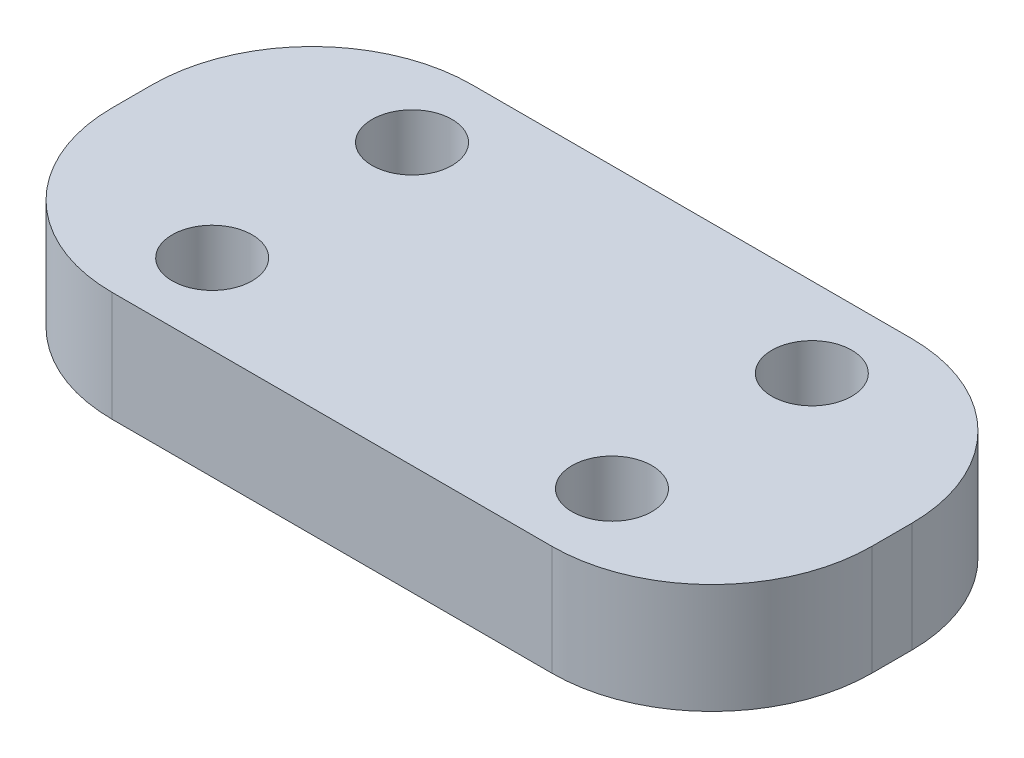
SolidWorks part; units mm, degrees
material "PETG-cf"
ref_plane "Plano frontal" through (0, 0, 0) normal (0, 0, 1) x (1, 0, 0)
ref_plane "Plano superior" through (0, 0, 0) normal (0, 1, 0) x (1, 0, 0)
ref_plane "Plano direito" through (0, 0, 0) normal (1, 0, 0) x (0, 0, -1)
sketch "Esboço1" plane through (0, 0, 0) normal (0, 1, 0) x (1, 0, 0)
  line L0 (-19, 0) -> (19, 0) construction
  line L1 (-19, -4) -> (19, -4)
  line L2 (-19, -4) -> (-19, 4)
  line L4 (19, -4) -> (19, 4)
  line L5 (-19, -4) -> (19, 4) construction
  line L6 (-19, 4) -> (19, -4) construction
  line L7 (0, 4) -> (0, -4) construction
  line L8 (-19, 4) -> (-19, 14)
  line L9 (-19, 14) -> (19, 14)
  line L10 (19, 14) -> (19, 4)
  line L11 (-10, 10) -> (10, 10) construction
  line L12 (-10, 0) -> (-10, 10) construction
  line L13 (10, 0) -> (10, 10) construction
  circle A0 centre (-10, 0) radius 2
  circle A1 centre (10, 0) radius 2
  circle A2 centre (-10, 10) radius 2
  circle A3 centre (10, 10) radius 2
  point P0 (0, 0)
  dimension "D3" = 4
  dimension "D6" = 4
  dimension "D1" = 38
  dimension "D2" = 8
  dimension "D4" = 20
  dimension "D5" = 10
extrude "Ressalto-extrusão1" add sketch "Esboço1" along normal mid plane 5.5
fillet "Filete1" radius 8 4 edges at (-19, 0, 4) (19, 0, 4) (-19, 0, -14) (19, 0, -14)
move or copy body "Corpo-Converter em corpo de malha1" [suppressed] bodies to move or copy 101 copy no translate (0, 0, 0) parameters "D1"=0, "D2"=0, "D3"=0
